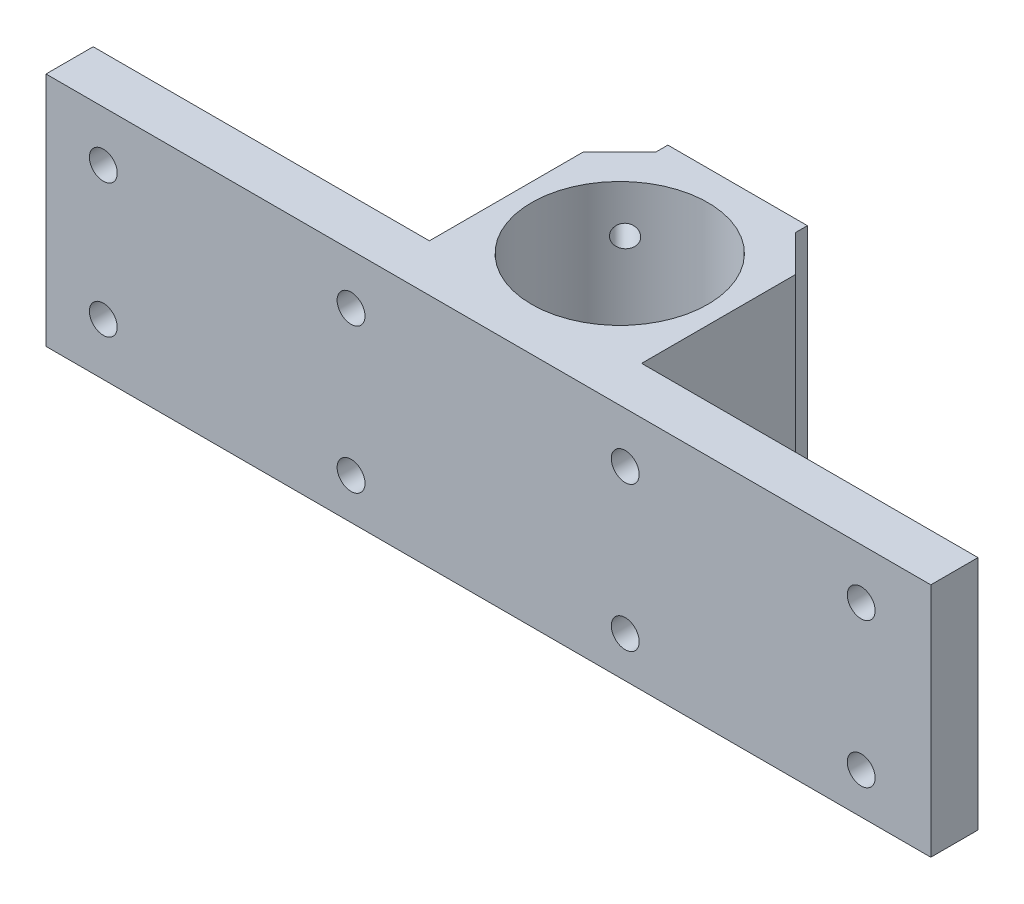
SolidWorks part; units mm, degrees
ref_plane "Front Plane" through (0, 0, 0) normal (0, 0, 1) x (1, 0, 0)
ref_plane "Top Plane" through (0, 0, 0) normal (0, 1, 0) x (1, 0, 0)
ref_plane "Right Plane" through (0, 0, 0) normal (1, 0, 0) x (0, 0, -1)
sketch "Sketch1" plane through (0, 0, 0) normal (0, 0, 1) x (1, 0, 0)
  line L1 (-94.1406, 21.747) -> (96.3594, 21.747)
  line L2 (-94.1406, 21.747) -> (-94.1406, -29.053)
  line L3 (-94.1406, -29.053) -> (96.3594, -29.053)
  line L4 (96.3594, 21.747) -> (96.3594, -29.053)
  dimension "D1" = 190.5
  dimension "D2" = 50.8
extrude "Boss-Extrude1" add sketch "Sketch1" along normal blind 10.16
sketch "Sketch5" plane through (0, 21.747, 0) normal (0, 1, 0) x (1, 0, 0)
  line L0 (7.7134, 0) -> (7.7134, -10.16)
  line L1 (96.3594, 0) -> (-94.1406, 0) construction
  line L2 (96.3594, -10.16) -> (-94.1406, -10.16) construction
  line L3 (-5.4946, 0) -> (-5.4946, -10.16)
  point P8 (1.1094, 0)
  dimension "D1" = 6.604
  dimension "D2" = 6.604
sketch "Sketch6" plane through (0, 21.747, 0) normal (0, 1, 0) x (1, 0, 0)
  arc A0 (7.7134, 0) -> (-5.4946, 0) centre (1.1094, 10.8827) cw
extrude "Cut-Extrude1" cut sketch "Sketch6" against normal through all and the other way through all flip side to cut
sketch "Sketch7" plane through (0, 21.747, 0) normal (0, 1, 0) x (1, 0, 0)
  line L0 (1.0861, -4.7215) -> (1.0874, 18.1385)
  circle A1 centre (1.0874, 18.1385) radius 22.8473
  dimension "D1" = 22.86
extrude "Boss-Extrude2" add sketch "Sketch7" against normal through all contours A1
sketch "Sketch8" plane through (0, 21.747, 0) normal (0, 1, 0) x (1, 0, 0)
  circle A0 centre (1.0874, 18.1385) radius 18.9865
  dimension "D1" = 37.973
extrude "Cut-Extrude2" cut sketch "Sketch8" against normal blind 45.72
sketch "Sketch9" plane through (0, -23.973, 0) normal (0, 1, 0) x (1, 0, 0)
  circle A0 centre (1.0874, 18.1385) radius 7.9375
  circle A1 centre (1.0874, 18.1385) radius 18.9865 construction
  dimension "D1" = 15.875
  dimension "D2" = 0
extrude "Cut-Extrude3" cut sketch "Sketch9" against normal through all
sketch "Sketch12" plane through (0, 21.747, 0) normal (0, 1, 0) x (1, 0, 0)
  line L0 (23.9347, 18.1385) -> (23.9347, 0)
  line L1 (96.3594, 0) -> (14.9796, 0) construction
  line L2 (23.9347, 0) -> (14.9796, 0)
  line L3 (-21.7599, 18.1385) -> (-21.7599, 0)
  line L4 (-12.8048, 0) -> (-94.1406, 0) construction
  line L5 (-21.7599, 0) -> (-12.8048, 0)
  circle A0 centre (1.0874, 18.1385) radius 22.8473 construction
  arc A1 (14.9796, 0) -> (23.9347, 18.1385) centre (1.0874, 18.1385) ccw
  arc A2 (-12.8048, 0) -> (-21.7599, 18.1385) centre (1.0874, 18.1385) cw
extrude "Boss-Extrude3" add sketch "Sketch12" against normal up to surface (50.8 mm away) up to face at (1.0874, -29.053, -10.201)
sketch "Sketch13" plane through (0, 0, 0) normal (0, 0, -1) x (-1, 0, 0)
  circle A0 centre (81.7995, -17.8107) radius 3
  circle A1 centre (81.7995, 10.912) radius 3
  circle A2 centre (-81.3701, 10.912) radius 3
  circle A3 centre (-81.3701, -20.2552) radius 3
extrude "Cut-Extrude4" cut sketch "Sketch13" against normal through all
sketch "Sketch15" plane through (0, 0, 0) normal (0, 0, -1) x (-1, 0, 0)
  circle A0 centre (-30.5701, 10.912) radius 3
  circle A1 centre (-81.3701, 10.912) radius 3 construction
  circle A2 centre (28.4595, 10.912) radius 3
  circle A3 centre (81.7995, 10.912) radius 3 construction
  circle A4 centre (-30.5701, -20.2552) radius 3
  circle A5 centre (28.4595, -20.2552) radius 3
  dimension "D1" = 6
  dimension "D3" = 6
  dimension "D4" = 53.34
  dimension "D5" = 6
  dimension "D6" = 6
  dimension "D2" = 50.8
extrude "Cut-Extrude5" cut sketch "Sketch15" against normal through all
sketch "Sketch16" plane through (0, -29.053, 0) normal (0, -1, 0) x (1, 0, 0)
  line L0 (-21.7599, -18.1385) -> (-21.7599, -40.9857)
  line L1 (1.0874, -40.9857) -> (-21.7599, -40.9857)
  arc A0 (-21.7599, -18.1385) -> (23.9347, -18.1385) centre (1.0874, -18.1385) ccw construction
  arc A1 (-21.7599, -18.1385) -> (1.0874, -40.9857) centre (1.0874, -18.1385) ccw
extrude "Boss-Extrude4" add sketch "Sketch16" against normal up to surface (50.8 mm away) up to face at (1.0984, 21.747, -4.8505)
sketch "Sketch18" plane through (0, -29.053, 0) normal (0, -1, 0) x (1, 0, 0)
  line L0 (23.9347, -18.1385) -> (23.9347, -40.9857)
  line L1 (23.9347, -40.9857) -> (1.0874, -40.9857)
  arc A0 (23.9347, -18.1385) -> (1.0874, -40.9857) centre (1.0874, -18.1385) cw
extrude "Boss-Extrude5" add sketch "Sketch18" against normal up to surface (50.8 mm away) up to face at (1.6229, 21.747, -9.3913)
sketch "Sketch19" plane through (0, 21.747, 0) normal (0, 1, 0) x (1, 0, 0)
  line L0 (23.9347, 33.1609) -> (16.1098, 40.9857)
  line L1 (23.9347, 0) -> (23.9347, 40.9857) construction
  line L2 (23.9347, 40.9857) -> (-21.7599, 40.9857) construction
  line L3 (16.1098, 40.9857) -> (23.9347, 40.9857)
  line L4 (23.9347, 40.9857) -> (23.9347, 33.1609)
  line L5 (-21.7599, 33.1609) -> (-13.935, 40.9857)
  line L6 (-21.7599, 40.9857) -> (-21.7599, 0) construction
  line L7 (-13.935, 40.9857) -> (-21.7599, 40.9857)
  line L8 (-21.7599, 40.9857) -> (-21.7599, 33.1609)
extrude "Cut-Extrude6" cut sketch "Sketch19" against normal through all
sketch "Sketch20" plane through (28.5478, 0, -28.5478) normal (0.7071, 0, -0.7071) x (-0.7071, 0, -0.7071)
  line L0 (17.5899, -29.053) -> (17.5899, 21.747) construction
  line L1 (17.5899, 21.747) -> (6.5239, 21.747) construction
  circle A0 centre (11.2399, 11.587) radius 2.3813
  circle A1 centre (11.2399, -16.988) radius 2.3813
  dimension "D1" = 4.7625
  dimension "D3" = 4.7625
  dimension "D4" = 6.35
  dimension "D2" = 6.35
  dimension "D5" = 28.575
  dimension "D6" = 10.16
extrude "Cut-Extrude7" cut sketch "Sketch20" against normal blind 10.16
sketch "Sketch21" plane through (-27.4604, 0, -27.4604) normal (-0.7071, 0, -0.7071) x (-0.7071, 0, 0.7071)
  line L0 (-8.0618, 21.747) -> (-19.1277, 21.747) construction
  line L1 (-8.0618, -29.053) -> (-8.0618, 21.747) construction
  circle A0 centre (-14.4118, 11.587) radius 2.3812
  circle A1 centre (-14.4118, -16.988) radius 2.3813
  dimension "D1" = 4.7625
  dimension "D2" = 4.7625
  dimension "D3" = 28.575
  dimension "D4" = 10.16
  dimension "D5" = 6.35
extrude "Cut-Extrude8" cut sketch "Sketch21" against normal blind 10.16
sketch "Sketch22" plane through (0, 0, -40.9857) normal (0, 0, -1) x (-1, 0, 0)
  line L1 (-16.1098, 21.747) -> (13.935, 21.747)
  line L2 (-16.1098, 21.747) -> (-16.1098, -29.053)
  line L3 (-16.1098, -29.053) -> (13.935, -29.053)
  line L4 (13.935, 21.747) -> (13.935, -29.053)
extrude "Boss-Extrude6" add sketch "Sketch22" along normal blind 2.54
